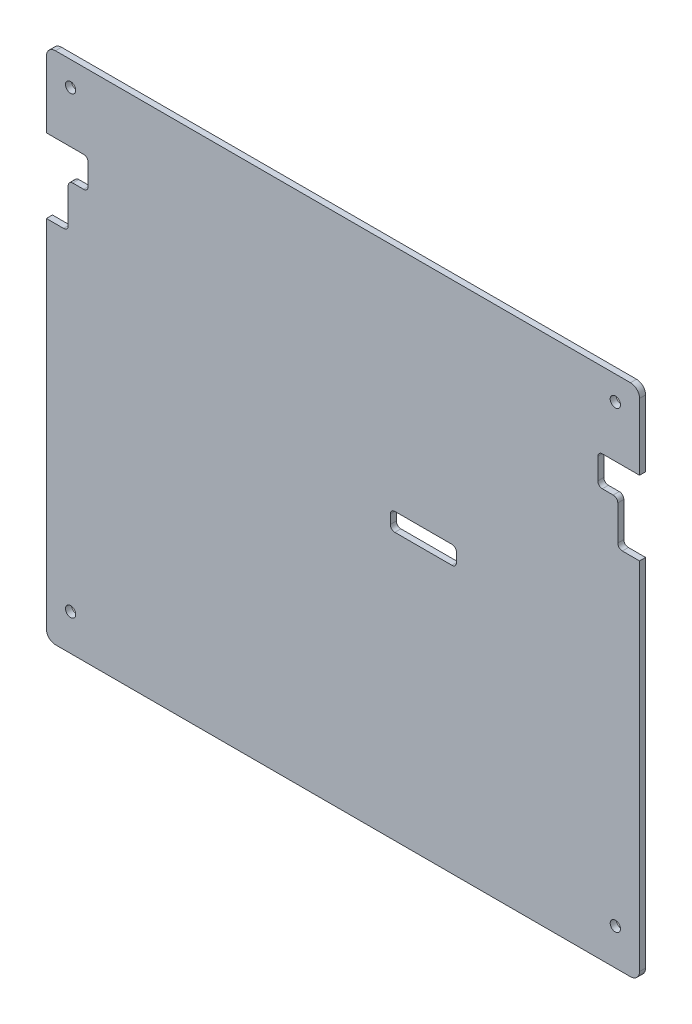
SolidWorks part; units mm, degrees
ref_plane "Спереди" through (0, 0, 0) normal (0, 0, 1) x (1, 0, 0)
ref_plane "Сверху" through (0, 0, 0) normal (0, 1, 0) x (1, 0, 0)
ref_plane "Справа" through (0, 0, 0) normal (1, 0, 0) x (0, 0, -1)
other "Configuration Table"
sketch "Hinge_clearance_0_profile" plane through (0, 0, 0) normal (0, 0, 1) x (1, 0, 0)
  line L0 (-4, 113.5) -> (8.8, 113.5)
  line L1 (10.8, 115.5) -> (10.8, 130.5)
  line L2 (8.8, 132.5) -> (-4, 132.5)
  line L3 (-6, 130.5) -> (-6, 115.5)
  arc A0 (8.8, 113.5) -> (10.8, 115.5) centre (8.8, 115.5) ccw
  arc A1 (10.8, 130.5) -> (8.8, 132.5) centre (8.8, 130.5) ccw
  arc A2 (-4, 132.5) -> (-6, 130.5) centre (-4, 130.5) ccw
  arc A3 (-6, 115.5) -> (-4, 113.5) centre (-4, 115.5) ccw
sketch "Hinge_clearance_1_profile" plane through (0, 0, 0) normal (0, 0, 1) x (1, 0, 0)
  line L0 (181.2, 113.5) -> (194, 113.5)
  line L1 (196, 115.5) -> (196, 130.5)
  line L2 (194, 132.5) -> (181.2, 132.5)
  line L3 (179.2, 130.5) -> (179.2, 115.5)
  arc A0 (194, 113.5) -> (196, 115.5) centre (194, 115.5) ccw
  arc A1 (196, 130.5) -> (194, 132.5) centre (194, 130.5) ccw
  arc A2 (181.2, 132.5) -> (179.2, 130.5) centre (181.2, 130.5) ccw
  arc A3 (179.2, 115.5) -> (181.2, 113.5) centre (181.2, 115.5) ccw
sketch "M3_clearance_0_profile" plane through (0, 0, 0) normal (0, 0, 1) x (1, 0, 0)
  circle A0 centre (5, 5) radius 1.7
sketch "M3_clearance_1_profile" plane through (0, 0, 0) normal (0, 0, 1) x (1, 0, 0)
  circle A0 centre (185, 5) radius 1.7
sketch "M3_clearance_2_profile" plane through (0, 0, 0) normal (0, 0, 1) x (1, 0, 0)
  circle A0 centre (5, 155) radius 1.7
sketch "M3_clearance_3_profile" plane through (0, 0, 0) normal (0, 0, 1) x (1, 0, 0)
  circle A0 centre (185, 155) radius 1.7
sketch "Keys_access_R1_5_profile" plane through (0, 0, 0) normal (0, 0, 1) x (1, 0, 0)
  line L0 (112.125, 81.25) -> (131, 81.25)
  line L1 (132.5, 82.75) -> (132.5, 85.75)
  line L2 (131, 87.25) -> (112.125, 87.25)
  line L3 (110.625, 85.75) -> (110.625, 82.75)
  arc A0 (131, 81.25) -> (132.5, 82.75) centre (131, 82.75) ccw
  arc A1 (132.5, 85.75) -> (131, 87.25) centre (131, 85.75) ccw
  arc A2 (112.125, 87.25) -> (110.625, 85.75) centre (112.125, 85.75) ccw
  arc A3 (110.625, 82.75) -> (112.125, 81.25) centre (112.125, 82.75) ccw
sketch "Эскиз2" plane through (0, 0, 0) normal (0, 0, 1) x (1, 0, 0)
  line L0 (-4.5, 113.5) -> (2.7, 113.5)
  line L1 (4.2, 115) -> (4.2, 149)
  line L2 (2.7, 150.5) -> (-4.5, 150.5)
  line L3 (-6, 149) -> (-6, 115)
  arc A0 (2.7, 113.5) -> (4.2, 115) centre (2.7, 115) ccw
  arc A1 (4.2, 149) -> (2.7, 150.5) centre (2.7, 149) ccw
  arc A2 (-4.5, 150.5) -> (-6, 149) centre (-4.5, 149) ccw
  arc A3 (-6, 115) -> (-4.5, 113.5) centre (-4.5, 115) ccw
sketch "Hinge_assembly_window_0_profile" plane through (0, 0, 0) normal (0, 0, 1) x (1, 0, 0)
  line L0 (-4.5, 132) -> (9.3, 132)
  line L1 (10.8, 133.5) -> (10.8, 149)
  line L2 (9.3, 150.5) -> (-4.5, 150.5)
  line L3 (-6, 149) -> (-6, 133.5)
  arc A0 (9.3, 132) -> (10.8, 133.5) centre (9.3, 133.5) ccw
  arc A1 (10.8, 149) -> (9.3, 150.5) centre (9.3, 149) ccw
  arc A2 (-4.5, 150.5) -> (-6, 149) centre (-4.5, 149) ccw
  arc A3 (-6, 133.5) -> (-4.5, 132) centre (-4.5, 133.5) ccw
sketch "Эскиз4" plane through (0, 0, 0) normal (0, 0, 1) x (1, 0, 0)
  line L0 (187.3, 113.5) -> (194.5, 113.5)
  line L1 (196, 115) -> (196, 149)
  line L2 (194.5, 150.5) -> (187.3, 150.5)
  line L3 (185.8, 149) -> (185.8, 115)
  arc A0 (194.5, 113.5) -> (196, 115) centre (194.5, 115) ccw
  arc A1 (196, 149) -> (194.5, 150.5) centre (194.5, 149) ccw
  arc A2 (187.3, 150.5) -> (185.8, 149) centre (187.3, 149) ccw
  arc A3 (185.8, 115) -> (187.3, 113.5) centre (187.3, 115) ccw
sketch "Hinge_assembly_window_1_profile" plane through (0, 0, 0) normal (0, 0, 1) x (1, 0, 0)
  line L0 (180.7, 132) -> (194.5, 132)
  line L1 (196, 133.5) -> (196, 149)
  line L2 (194.5, 150.5) -> (180.7, 150.5)
  line L3 (179.2, 149) -> (179.2, 133.5)
  arc A0 (194.5, 132) -> (196, 133.5) centre (194.5, 133.5) ccw
  arc A1 (196, 149) -> (194.5, 150.5) centre (194.5, 149) ccw
  arc A2 (180.7, 150.5) -> (179.2, 149) centre (180.7, 149) ccw
  arc A3 (179.2, 133.5) -> (180.7, 132) centre (180.7, 133.5) ccw
sketch "Эскиз6" plane through (0, 0, 0) normal (0, 0, 1) x (1, 0, 0)
  circle A0 centre (5, 5) radius 1.7
sketch "Эскиз7" plane through (0, 0, 0) normal (0, 0, 1) x (1, 0, 0)
  circle A0 centre (185, 5) radius 1.7
sketch "Эскиз8" plane through (0, 0, 0) normal (0, 0, 1) x (1, 0, 0)
  circle A0 centre (5, 155) radius 1.7
sketch "Эскиз9" plane through (0, 0, 0) normal (0, 0, 1) x (1, 0, 0)
  circle A0 centre (185, 155) radius 1.7
sketch "Эскиз10" plane through (0, 0, 0) normal (0, 0, 1) x (1, 0, 0)
  line L0 (112.125, 81.25) -> (131, 81.25)
  line L1 (132.5, 82.75) -> (132.5, 85.75)
  line L2 (131, 87.25) -> (112.125, 87.25)
  line L3 (110.625, 85.75) -> (110.625, 82.75)
  arc A0 (131, 81.25) -> (132.5, 82.75) centre (131, 82.75) ccw
  arc A1 (132.5, 85.75) -> (131, 87.25) centre (131, 85.75) ccw
  arc A2 (112.125, 87.25) -> (110.625, 85.75) centre (112.125, 85.75) ccw
  arc A3 (110.625, 82.75) -> (112.125, 81.25) centre (112.125, 82.75) ccw
sketch "Эскиз12" plane through (0, 0, 0) normal (0, 0, 1) x (1, 0, 0)
  line L0 (-4.5, 113.5) -> (2.7, 113.5)
  line L1 (4.2, 115) -> (4.2, 130.5)
  line L2 (5.7, 132) -> (9.3, 132)
  line L3 (10.8, 133.5) -> (10.8, 149)
  line L4 (9.3, 150.5) -> (-4.5, 150.5)
  line L5 (-6, 149) -> (-6, 115)
  arc A0 (-6, 115) -> (-4.5, 113.5) centre (-4.5, 115) ccw
  arc A1 (2.7, 113.5) -> (4.2, 115) centre (2.7, 115) ccw
  arc A2 (4.2, 130.5) -> (5.7, 132) centre (5.7, 130.5) cw
  arc A3 (9.3, 132) -> (10.8, 133.5) centre (9.3, 133.5) ccw
  arc A4 (10.8, 149) -> (9.3, 150.5) centre (9.3, 149) ccw
  arc A5 (-4.5, 150.5) -> (-6, 149) centre (-4.5, 149) ccw
sketch "Эскиз13" plane through (0, 0, 0) normal (0, 0, 1) x (1, 0, 0)
  line L0 (194.5, 113.5) -> (187.3, 113.5)
  line L1 (185.8, 115) -> (185.8, 130.5)
  line L2 (184.3, 132) -> (180.7, 132)
  line L3 (179.2, 133.5) -> (179.2, 149)
  line L4 (180.7, 150.5) -> (194.5, 150.5)
  line L5 (196, 149) -> (196, 115)
  arc A0 (196, 115) -> (194.5, 113.5) centre (194.5, 115) cw
  arc A1 (187.3, 113.5) -> (185.8, 115) centre (187.3, 115) cw
  arc A2 (185.8, 130.5) -> (184.3, 132) centre (184.3, 130.5) ccw
  arc A3 (180.7, 132) -> (179.2, 133.5) centre (180.7, 133.5) cw
  arc A4 (179.2, 149) -> (180.7, 150.5) centre (180.7, 149) cw
  arc A5 (194.5, 150.5) -> (196, 149) centre (194.5, 149) cw
sketch "Эскиз14" plane through (0, 0, 0) normal (0, 0, 1) x (1, 0, 0)
  circle A0 centre (5, 5) radius 1.7
sketch "Эскиз15" plane through (0, 0, 0) normal (0, 0, 1) x (1, 0, 0)
  circle A0 centre (185, 5) radius 1.7
sketch "Эскиз16" plane through (0, 0, 0) normal (0, 0, 1) x (1, 0, 0)
  circle A0 centre (5, 155) radius 1.7
sketch "Эскиз17" plane through (0, 0, 0) normal (0, 0, 1) x (1, 0, 0)
  circle A0 centre (185, 155) radius 1.7
sketch "Эскиз18" plane through (0, 0, 0) normal (0, 0, 1) x (1, 0, 0)
  line L0 (112.125, 81.25) -> (131, 81.25)
  line L1 (132.5, 82.75) -> (132.5, 85.75)
  line L2 (131, 87.25) -> (112.125, 87.25)
  line L3 (110.625, 85.75) -> (110.625, 82.75)
  arc A0 (131, 81.25) -> (132.5, 82.75) centre (131, 82.75) ccw
  arc A1 (132.5, 85.75) -> (131, 87.25) centre (131, 85.75) ccw
  arc A2 (112.125, 87.25) -> (110.625, 85.75) centre (112.125, 85.75) ccw
  arc A3 (110.625, 82.75) -> (112.125, 81.25) centre (112.125, 82.75) ccw
sketch "Эскиз20" plane through (0, 0, 0) normal (0, 0, 1) x (1, 0, 0)
  line L0 (-4.5, 113.5) -> (2.7, 113.5)
  line L1 (4.2, 115) -> (4.2, 127.5)
  line L2 (5.7, 129) -> (9.3, 129)
  line L3 (10.8, 130.5) -> (10.8, 135.5)
  line L4 (9.3, 137) -> (-4.5, 137)
  line L5 (-6, 135.5) -> (-6, 115)
  arc A0 (-6, 115) -> (-4.5, 113.5) centre (-4.5, 115) ccw
  arc A1 (2.7, 113.5) -> (4.2, 115) centre (2.7, 115) ccw
  arc A2 (4.2, 127.5) -> (5.7, 129) centre (5.7, 127.5) cw
  arc A3 (9.3, 129) -> (10.8, 130.5) centre (9.3, 130.5) ccw
  arc A4 (10.8, 135.5) -> (9.3, 137) centre (9.3, 135.5) ccw
  arc A5 (-4.5, 137) -> (-6, 135.5) centre (-4.5, 135.5) ccw
sketch "Эскиз21" plane through (0, 0, 0) normal (0, 0, 1) x (1, 0, 0)
  line L0 (194.5, 113.5) -> (187.3, 113.5)
  line L1 (185.8, 115) -> (185.8, 127.5)
  line L2 (184.3, 129) -> (180.7, 129)
  line L3 (179.2, 130.5) -> (179.2, 135.5)
  line L4 (180.7, 137) -> (194.5, 137)
  line L5 (196, 135.5) -> (196, 115)
  arc A0 (196, 115) -> (194.5, 113.5) centre (194.5, 115) cw
  arc A1 (187.3, 113.5) -> (185.8, 115) centre (187.3, 115) cw
  arc A2 (185.8, 127.5) -> (184.3, 129) centre (184.3, 127.5) ccw
  arc A3 (180.7, 129) -> (179.2, 130.5) centre (180.7, 130.5) cw
  arc A4 (179.2, 135.5) -> (180.7, 137) centre (180.7, 135.5) cw
  arc A5 (194.5, 137) -> (196, 135.5) centre (194.5, 135.5) cw
sketch "Эскиз22" plane through (0, 0, 0) normal (0, 0, 1) x (1, 0, 0)
  circle A0 centre (5, 5) radius 1.7
sketch "Эскиз23" plane through (0, 0, 0) normal (0, 0, 1) x (1, 0, 0)
  circle A0 centre (185, 5) radius 1.7
sketch "Эскиз24" plane through (0, 0, 0) normal (0, 0, 1) x (1, 0, 0)
  circle A0 centre (5, 155) radius 1.7
sketch "Эскиз25" plane through (0, 0, 0) normal (0, 0, 1) x (1, 0, 0)
  circle A0 centre (185, 155) radius 1.7
sketch "Эскиз26" plane through (0, 0, 0) normal (0, 0, 1) x (1, 0, 0)
  line L0 (112.125, 81.25) -> (131, 81.25)
  line L1 (132.5, 82.75) -> (132.5, 85.75)
  line L2 (131, 87.25) -> (112.125, 87.25)
  line L3 (110.625, 85.75) -> (110.625, 82.75)
  arc A0 (131, 81.25) -> (132.5, 82.75) centre (131, 82.75) ccw
  arc A1 (132.5, 85.75) -> (131, 87.25) centre (131, 85.75) ccw
  arc A2 (112.125, 87.25) -> (110.625, 85.75) centre (112.125, 85.75) ccw
  arc A3 (110.625, 82.75) -> (112.125, 81.25) centre (112.125, 82.75) ccw
sketch "Acrylic_2mm_profile" plane through (0, 0, 0) normal (0, 0, 1) x (1, 0, 0)
  line L0 (0, -7) -> (190, -7)
  line L1 (193, -4) -> (193, 160)
  line L2 (190, 163) -> (0, 163)
  line L3 (-3, 160) -> (-3, -4)
  arc A0 (190, -7) -> (193, -4) centre (190, -4) ccw
  arc A1 (193, 160) -> (190, 163) centre (190, 160) ccw
  arc A2 (0, 163) -> (-3, 160) centre (0, 160) ccw
  arc A3 (-3, -4) -> (0, -7) centre (0, -4) ccw
extrude "Acrylic_2mm" add sketch "Acrylic_2mm_profile" along normal blind 2 from offset 12 offset against normal yes
sketch "Эскиз28" plane through (0, 0, 0) normal (0, 0, 1) x (1, 0, 0)
  line L0 (-4.5, 113.5) -> (2.7, 113.5)
  line L1 (4.2, 115) -> (4.2, 126.5)
  line L2 (5.7, 128) -> (9.3, 128)
  line L3 (10.8, 129.5) -> (10.8, 136.5)
  line L4 (9.3, 138) -> (-4.5, 138)
  line L5 (-6, 136.5) -> (-6, 115)
  arc A0 (-6, 115) -> (-4.5, 113.5) centre (-4.5, 115) ccw
  arc A1 (2.7, 113.5) -> (4.2, 115) centre (2.7, 115) ccw
  arc A2 (4.2, 126.5) -> (5.7, 128) centre (5.7, 126.5) cw
  arc A3 (9.3, 128) -> (10.8, 129.5) centre (9.3, 129.5) ccw
  arc A4 (10.8, 136.5) -> (9.3, 138) centre (9.3, 136.5) ccw
  arc A5 (-4.5, 138) -> (-6, 136.5) centre (-4.5, 136.5) ccw
extrude "Hinge_clearance_0" cut sketch "Эскиз28" against normal blind 2.4 from offset 9.8 offset against normal yes
sketch "Эскиз29" plane through (0, 0, 0) normal (0, 0, 1) x (1, 0, 0)
  line L0 (194.5, 113.5) -> (187.3, 113.5)
  line L1 (185.8, 115) -> (185.8, 126.5)
  line L2 (184.3, 128) -> (180.7, 128)
  line L3 (179.2, 129.5) -> (179.2, 136.5)
  line L4 (180.7, 138) -> (194.5, 138)
  line L5 (196, 136.5) -> (196, 115)
  arc A0 (196, 115) -> (194.5, 113.5) centre (194.5, 115) cw
  arc A1 (187.3, 113.5) -> (185.8, 115) centre (187.3, 115) cw
  arc A2 (185.8, 126.5) -> (184.3, 128) centre (184.3, 126.5) ccw
  arc A3 (180.7, 128) -> (179.2, 129.5) centre (180.7, 129.5) cw
  arc A4 (179.2, 136.5) -> (180.7, 138) centre (180.7, 136.5) cw
  arc A5 (194.5, 138) -> (196, 136.5) centre (194.5, 136.5) cw
extrude "Hinge_clearance_1" cut sketch "Эскиз29" against normal blind 2.4 from offset 9.8 offset against normal yes
sketch "Эскиз30" plane through (0, 0, 0) normal (0, 0, 1) x (1, 0, 0)
  circle A0 centre (5, 5) radius 1.7
extrude "M3_clearance_0" cut sketch "Эскиз30" against normal blind 2.4 from offset 9.8 offset against normal yes
sketch "Эскиз31" plane through (0, 0, 0) normal (0, 0, 1) x (1, 0, 0)
  circle A0 centre (185, 5) radius 1.7
extrude "M3_clearance_1" cut sketch "Эскиз31" against normal blind 2.4 from offset 9.8 offset against normal yes
sketch "Эскиз32" plane through (0, 0, 0) normal (0, 0, 1) x (1, 0, 0)
  circle A0 centre (5, 155) radius 1.7
extrude "M3_clearance_2" cut sketch "Эскиз32" against normal blind 2.4 from offset 9.8 offset against normal yes
sketch "Эскиз33" plane through (0, 0, 0) normal (0, 0, 1) x (1, 0, 0)
  circle A0 centre (185, 155) radius 1.7
extrude "M3_clearance_3" cut sketch "Эскиз33" against normal blind 2.4 from offset 9.8 offset against normal yes
sketch "Эскиз34" plane through (0, 0, 0) normal (0, 0, 1) x (1, 0, 0)
  line L0 (112.125, 81.25) -> (131, 81.25)
  line L1 (132.5, 82.75) -> (132.5, 85.75)
  line L2 (131, 87.25) -> (112.125, 87.25)
  line L3 (110.625, 85.75) -> (110.625, 82.75)
  arc A0 (131, 81.25) -> (132.5, 82.75) centre (131, 82.75) ccw
  arc A1 (132.5, 85.75) -> (131, 87.25) centre (131, 85.75) ccw
  arc A2 (112.125, 87.25) -> (110.625, 85.75) centre (112.125, 85.75) ccw
  arc A3 (110.625, 82.75) -> (112.125, 81.25) centre (112.125, 82.75) ccw
extrude "Keys_access_R1_5" cut sketch "Эскиз34" against normal blind 2.4 from offset 9.8 offset against normal yes
